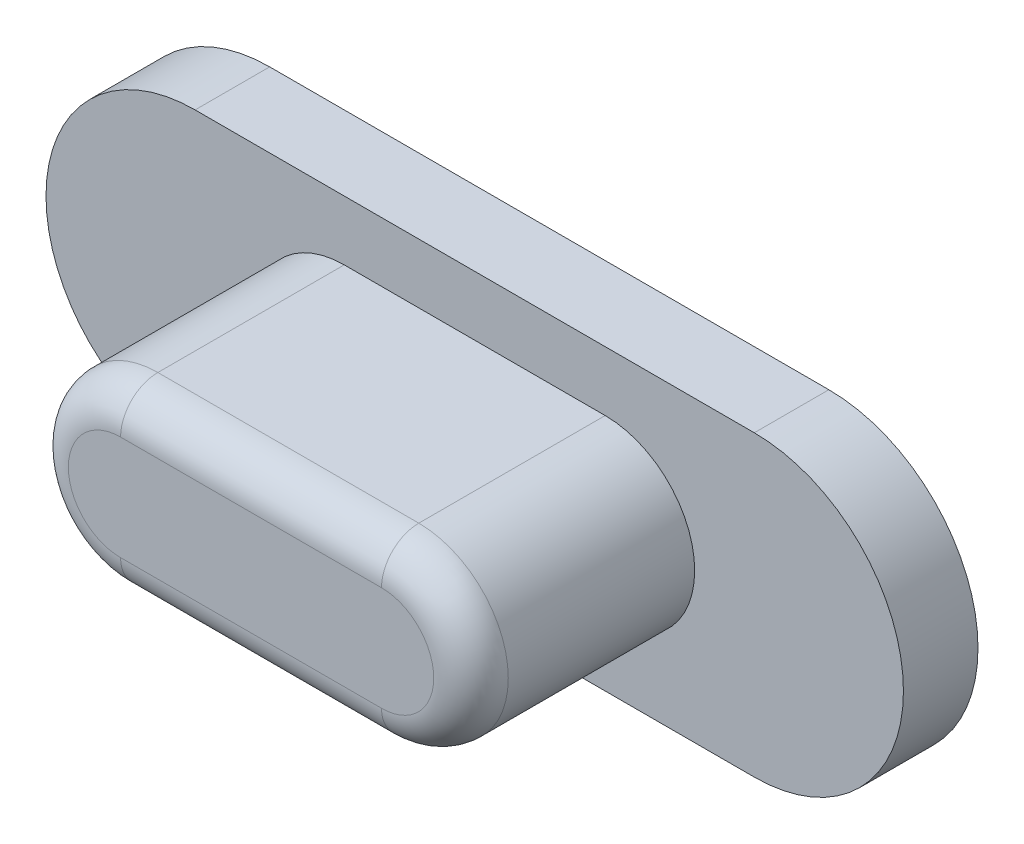
SolidWorks part; units mm, degrees
ref_plane "前视基准面" through (0, 0, 0) normal (0, 0, 1) x (1, 0, 0)
ref_plane "上视基准面" through (0, 0, 0) normal (0, 1, 0) x (1, 0, 0)
ref_plane "右视基准面" through (0, 0, 0) normal (1, 0, 0) x (0, 0, -1)
sketch "草图1" plane through (0, 0, 0) normal (0, 0, 1) x (1, 0, 0)
  line L0 (1.25, 2.5) -> (4.75, 2.5) construction
  line L1 (0, 0) -> (6, 0) construction
  line L2 (0, 0) -> (0, 2.5) construction
  line L3 (0, 2.5) -> (6, 2.5) construction
  line L4 (6, 0) -> (6, 2.5) construction
  line L5 (4.75, 0) -> (1.25, 0) construction
  line L6 (1.25, 2.45) -> (4.75, 2.45)
  line L7 (4.75, 0.05) -> (1.25, 0.05)
  arc A0 (1.25, 2.5) -> (1.25, 0) centre (1.25, 1.25) ccw construction
  arc A1 (4.75, 0) -> (4.75, 2.5) centre (4.75, 1.25) ccw construction
  arc A2 (4.75, 0.05) -> (4.75, 2.45) centre (4.75, 1.25) ccw
  arc A3 (1.25, 2.45) -> (1.25, 0.05) centre (1.25, 1.25) ccw
  dimension "D1" = 6
  dimension "D2" = 2.5
  dimension "D3" = 0.05
extrude "凸台-拉伸1" add sketch "草图1" along normal blind 3
sketch "草图2" plane through (0, 0, 0) normal (0, 0, -1) x (-1, 0, 0)
  line L2 (-4.75, 0.05) -> (-1.25, 0.05)
  line L3 (-4.75, 0.05) -> (-1.25, 0.05)
  line L6 (0.75, 1.25) -> (-6.75, 1.25) construction
  line L7 (0.75, -0.75) -> (-6.75, -0.75)
  line L8 (-1.25, 2.45) -> (-4.75, 2.45)
  line L9 (-1.25, 2.45) -> (-4.75, 2.45)
  line L10 (0.75, 3.25) -> (-6.75, 3.25)
  arc A2 (-1.25, 0.05) -> (-1.25, 2.45) centre (-1.25, 1.25) ccw
  arc A3 (-1.25, 0.05) -> (-1.25, 2.45) centre (-1.25, 1.25) ccw
  arc A6 (0.75, -0.75) -> (0.75, 3.25) centre (0.75, 1.25) ccw
  arc A7 (-6.75, 3.25) -> (-6.75, -0.75) centre (-6.75, 1.25) ccw
  arc A8 (-4.75, 2.45) -> (-4.75, 0.05) centre (-4.75, 1.25) ccw
  arc A9 (-4.75, 2.45) -> (-4.75, 0.05) centre (-4.75, 1.25) ccw
  point P4 (-3, 1.25)
  arc M17 (-4.75, 2.45) -> (-4.75, 0.05) centre (-4.75, 1.25) ccw
  line M18 (-4.75, 0.05) -> (-1.25, 0.05)
  arc M19 (-1.25, 0.05) -> (-1.25, 2.45) centre (-1.25, 1.25) ccw
  line M20 (-1.25, 2.45) -> (-4.75, 2.45)
  dimension "D2" = 4
  dimension "D3" = 2
  dimension "D4" = 2
  dimension "D1" = 0
extrude "凸台-拉伸2" add sketch "草图2" along normal blind 1 contours L10 | M20 M17 M18 M19 region at (3, 1.25, 0) region at (3, -0.6282, 0)
fillet "圆角1" radius 0.5 4 edges at (0.05, 1.25, 3) (3, 0.05, 3) (5.95, 1.25, 3) (3, 2.45, 3)
